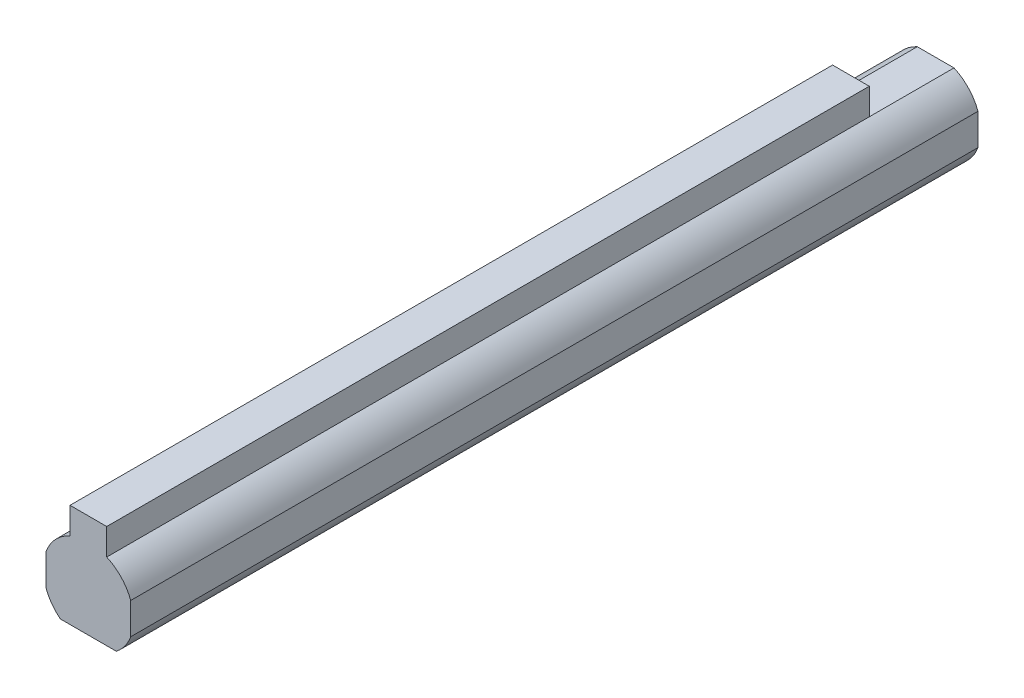
SolidWorks part; units mm, degrees
ref_plane "Front Plane" through (0, 0, 0) normal (0, 0, 1) x (1, 0, 0)
ref_plane "Top Plane" through (0, 0, 0) normal (0, 1, 0) x (1, 0, 0)
ref_plane "Right Plane" through (0, 0, 0) normal (1, 0, 0) x (0, 0, -1)
sketch "Sketch1" plane through (0, 0, 0) normal (0, 0, 1) x (1, 0, 0)
  line L0 (0, 0) -> (0, 12) construction
  line L1 (-3.25, 12) -> (3.25, 12)
  line L2 (-3.25, 12) -> (-3.25, 7.3101)
  line L3 (3.25, 12) -> (3.25, 7.3101)
  line L4 (-7.5, 0) -> (7.5, 0) construction
  line L5 (7.5, -2.7839) -> (7.5, 2.7839)
  line L6 (-7.5, -2.7839) -> (-7.5, 2.7839)
  line L7 (-3.25, 7.3101) -> (3.25, 7.3101)
  line L8 (0, 0) -> (0, -6.285) construction
  line L9 (4.9496, -6.285) -> (-4.9496, -6.285)
  arc A0 (-7.5, -2.7839) -> (7.5, -2.7839) centre (0, 0) ccw
  arc A1 (7.5, 2.7839) -> (3.25, 7.3101) centre (0, 0) ccw
  arc A2 (-3.25, 7.3101) -> (-7.5, 2.7839) centre (0, 0) ccw
  point P6 (0, 12)
  point P12 (0, 0)
  point P15 (7.5, 0)
  point P20 (0, -6.285)
  dimension "D1" = 16
  dimension "D2" = 12
  dimension "D3" = 6.5
  dimension "D4" = 15
  dimension "D5" = 18.285
extrude "Boss-Extrude1" add sketch "Sketch1" along normal blind 150 contours L7 A2 L6 A0 L5 A1 region at (0, 0.3172, 0)
extrude "Boss-Extrude2" add sketch "Sketch1<3>" against normal offset from surface (135 mm away) 15 from surface contours L2 L7 L3 L1 region at (0, 9.655, 0) up to face at (0, 0.3196, 0) starting at face at (0, 0.3196, 150)
sketch "Sketch1<3>" plane through (0, 0, 0) normal (0, 0, 1) x (1, 0, 0) same geometry as "Sketch1"
equation "\"D2@Sketch1\"=\"D1@Sketch1\"/2+4"
